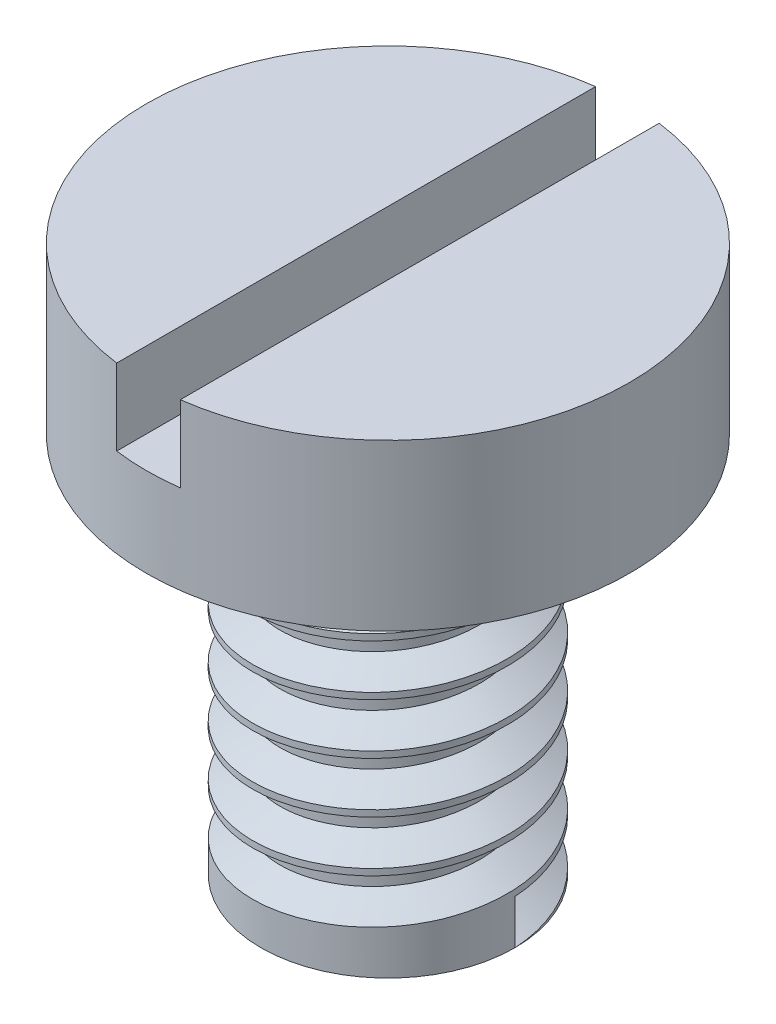
SolidWorks part; units mm, degrees
material "Brass"
ref_plane "Front Plane" through (0, 0, 0) normal (0, 0, 1) x (1, 0, 0)
ref_plane "Top Plane" through (0, 0, 0) normal (0, 1, 0) x (1, 0, 0)
ref_plane "Right Plane" through (0, 0, 0) normal (1, 0, 0) x (0, 0, -1)
sketch "Sketch1" plane through (0, 0, 0) normal (0, 1, 0) x (1, 0, 0)
  circle A0 centre (0, 0) radius 1.9
  dimension "D1" = 3.8
extrude "Boss-Extrude1" add sketch "Sketch1" along normal blind 1.3
sketch "Sketch2" plane through (0, 0, 0) normal (0, -1, 0) x (1, 0, 0)
  circle A0 centre (0, 0) radius 1
  dimension "D1" = 2
extrude "Boss-Extrude2" add sketch "Sketch2" along normal blind 3
thread "Thread1" pitch 0.4 method cut profile "Thread Profile1" start angle 0, offset 0, length 0, pitch 0.4, diameter 2
ref_plane "Plane1" through (1, -3, 0) normal (0, 0, 1) x (1, 0, 0)
sketch "Thread Profile1" plane through (1, -3, 0) normal (0, 0, 1) x (1, 0, 0)
  line L0 (0, 0) -> (0, 0.4) construction
  line L11 (0, 0) -> (0, 0.35)
  line L12 (0, 0.35) -> (-0.2165, 0.225)
  line L13 (-0.2165, 0.225) -> (-0.2165, 0.125)
  line L15 (-0.2165, 0.125) -> (0, 0)
  line L17 (-0.2165, 0.175) -> (0, 0.175) construction
  point P2 (0, 0)
  dimension "Pitch" = 0.4
  dimension "Profile_Angle" = 60
  dimension "Profile_Land" = 0.1
  dimension "Profile_Height" = 0.2165
sketch "Sketch6" plane through (0, 1.3, 0) normal (0, 1, 0) x (1, 0, 0)
  line L0 (0, -1000) -> (0, 49000) construction
  line L2 (0.25, -2) -> (-0.25, -2)
  line L3 (0.25, -2) -> (0.25, 2)
  line L4 (0.25, 2) -> (-0.25, 2)
  line L5 (-0.25, -2) -> (-0.25, 2)
  line L6 (0.25, -2) -> (-0.25, 2) construction
  line L7 (0.25, 2) -> (-0.25, -2) construction
  point P1 (0, 0)
  dimension "D1" = 0.5
  dimension "D2" = 4
extrude "Cut-Extrude1" cut sketch "Sketch6" against normal blind 0.6
